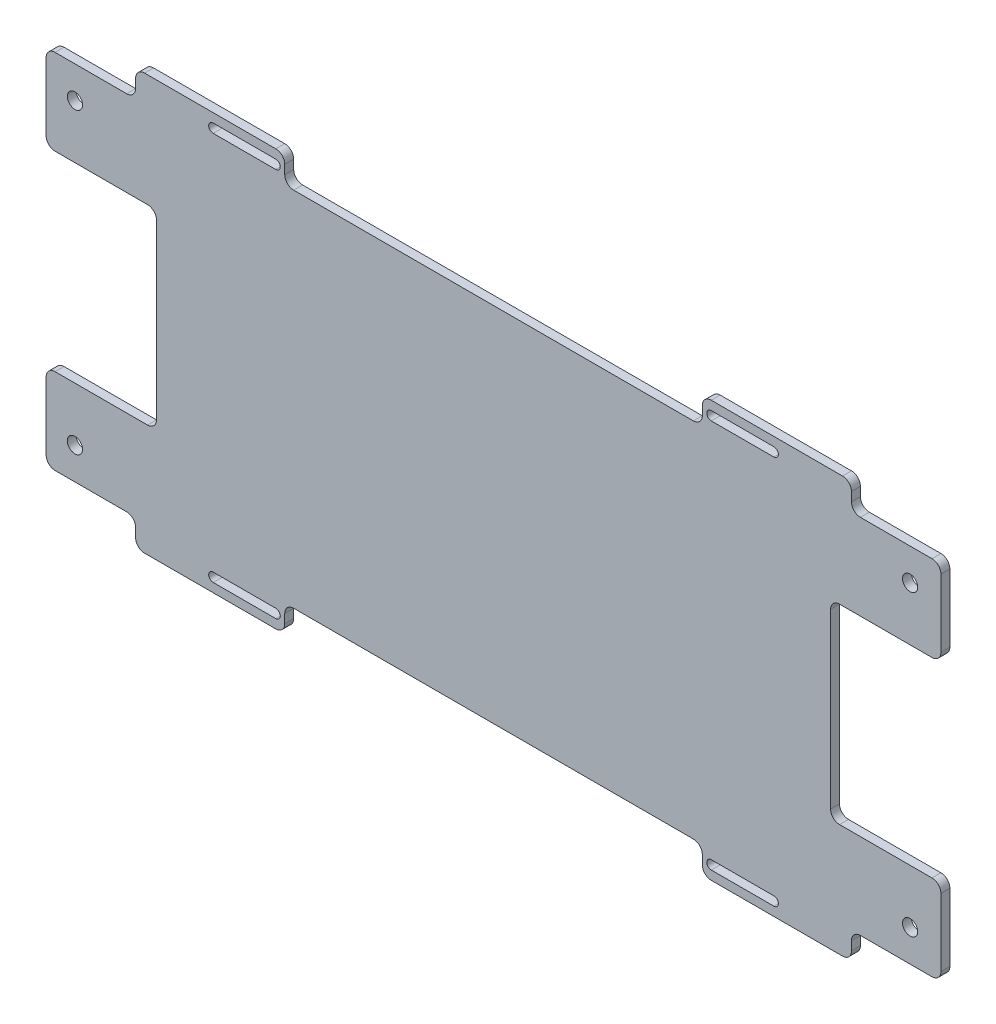
SolidWorks part; units mm, degrees
ref_plane "Front Plane" through (0, 0, 0) normal (0, 0, 1) x (1, 0, 0)
ref_plane "Top Plane" through (0, 0, 0) normal (0, 1, 0) x (1, 0, 0)
ref_plane "Right Plane" through (0, 0, 0) normal (1, 0, 0) x (0, 0, -1)
sketch "Sketch1" plane through (0, 0, 0) normal (0, 0, 1) x (1, 0, 0)
  line L0 (178.3692, 60.7015) -> (-178.3692, 60.7015) construction
  line L1 (-150, -60.7015) -> (150, -60.7015)
  line L2 (-150, -60.7015) -> (-150, 60.7015)
  line L3 (-150, 60.7015) -> (150, 60.7015)
  line L4 (150, -60.7015) -> (150, 60.7015)
  line L5 (-150, -60.7015) -> (150, 60.7015) construction
  line L6 (-150, 60.7015) -> (150, -60.7015) construction
  point P0 (0, 0)
  dimension "D1" = 300
extrude "Boss-Extrude1" add sketch "Sketch1" along normal blind 3 contours L3 L4 L1 L2
sketch "Sketch2" plane through (0, 0, 3) normal (0, 0, 1) x (1, 0, 0)
  line L0 (-125, 30) -> (-175, 30) construction
  line L1 (-164.146, -32) -> (-113, -32)
  line L2 (-164.146, -32) -> (-164.146, 32)
  line L3 (-164.146, 32) -> (-113, 32)
  line L4 (-113, -32) -> (-113, 32)
  line L5 (-164.146, -32) -> (-113, 32) construction
  line L6 (-164.146, 32) -> (-113, -32) construction
  line L7 (-115, -20) -> (-115, 20) construction
  point P0 (-138.573, 0)
  point P5 (0, 0)
  dimension "D1" = 2
  dimension "D3" = 2
extrude "Cut-Extrude1" cut sketch "Sketch2" against normal up to surface (3 mm away) up to face at (0, 0, 0)
mirror "Mirror1" about plane through (0, 0, 0) normal (1, 0, 0) of "Cut-Extrude1"
sketch "Sketch3" plane through (0, 0, 3) normal (0, 0, 1) x (1, 0, 0)
  line L0 (-150, -60.7015) -> (150, -60.7015) construction
  line L1 (-120, -60.7015) -> (-70, -60.7015)
  line L2 (-120, -60.7015) -> (-120, -69.7015)
  line L3 (-120, -69.7015) -> (-70, -69.7015)
  line L4 (-70, -60.7015) -> (-70, -69.7015)
  line L5 (-94, -65.2015) -> (-73, -65.2015) construction
  line L6 (-94, -63.7015) -> (-73, -63.7015)
  line L7 (-94, -66.7015) -> (-73, -66.7015)
  arc A0 (-94, -63.7015) -> (-94, -66.7015) centre (-94, -65.2015) ccw
  arc A1 (-73, -66.7015) -> (-73, -63.7015) centre (-73, -65.2015) ccw
  point P8 (-83.5, -65.2015)
  point P13 (0, 0)
  point P14 (-81.3809, -63.7015)
  point P17 (-120, -65.2015)
  dimension "D3" = 70
  dimension "D1" = 50
  dimension "D2" = 9
  dimension "D4" = 3
extrude "Boss-Extrude2" add sketch "Sketch3" against normal up to surface (3 mm away) up to face at (0, 0, 0)
mirror "Mirror3" about plane through (0, 0, 0) normal (0, 1, 0) of "Boss-Extrude2"
mirror "Mirror4" about plane through (0, 0, 0) normal (1, 0, 0) of "Mirror3", "Boss-Extrude2"
fillet "Fillet2" radius 3 16 edges at (-120, 60.7015, 1.5) (-120, 69.7015, 1.5) (-70, 69.7015, 1.5) (-70, 60.7015, 1.5) (70, 60.7015, 1.5) (70, 69.7015, 1.5) (120, 60.7015, 1.5) (120, 69.7015, 1.5) (70, -69.7015, 1.5) (70, -60.7015, 1.5) (120, -69.7015, 1.5) (120, -60.7015, 1.5) (-70, -69.7015, 1.5) (-70, -60.7015, 1.5) (-120, -69.7015, 1.5) (-120, -60.7015, 1.5)
fillet "Fillet3" radius 3 12 edges at (-113, -32, 1.5) (-150, 60.7015, 1.5) (-113, 32, 1.5) (-150, 32, 1.5) (-150, -60.7015, 1.5) (-150, -32, 1.5) (150, 60.7015, 1.5) (150, 32, 1.5) (113, 32, 1.5) (150, -32, 1.5) (113, -32, 1.5) (150, -60.7015, 1.5)
sketch "Sketch4" plane through (0, 0, 0) normal (0, 0, -1) x (-1, 0, 0)
  circle A0 centre (-139.6609, -50) radius 2.55
  circle A1 centre (-139.6609, 50) radius 2.55
  circle A2 centre (140.3391, -50) radius 2.55
  circle A3 centre (140.3391, 50) radius 2.55
  dimension "D1" = 5.1
  dimension "D2" = 5.1
  dimension "D3" = 5.1
  dimension "D4" = 5.1
extrude "Cut-Extrude2" cut sketch "Sketch4" against normal up to surface (3 mm away) up to face at (0, 0, 3)
